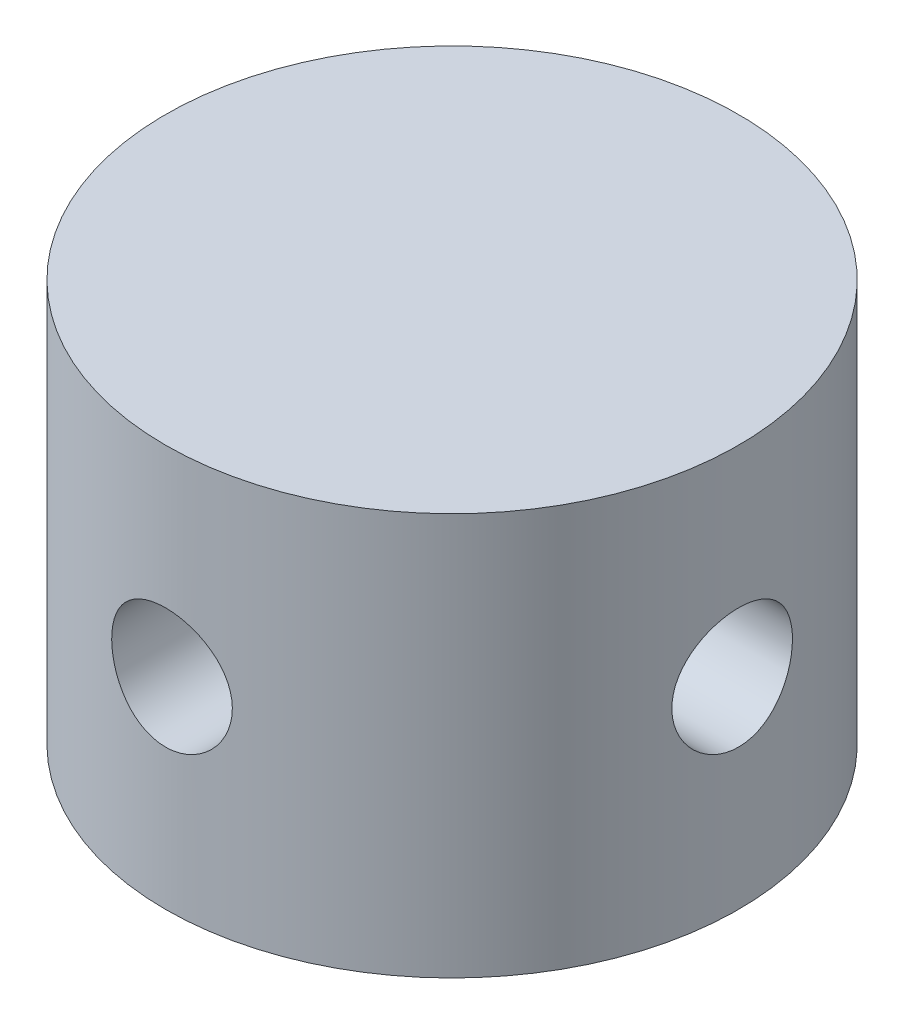
SolidWorks part; units mm, degrees
ref_plane "Front Plane" through (0, 0, 0) normal (0, 0, 1) x (1, 0, 0)
ref_plane "Top Plane" through (0, 0, 0) normal (0, 1, 0) x (1, 0, 0)
ref_plane "Right Plane" through (0, 0, 0) normal (1, 0, 0) x (0, 0, -1)
sketch "Sketch1" plane through (0, 0, 0) normal (0, 1, 0) x (1, 0, 0)
  circle A0 centre (0, 0) radius 14.25
  dimension "D1" = 28.5
extrude "Boss-Extrude1" add sketch "Sketch1" along normal blind 20
ref_plane "Plane1" through (14.25, 0, 0) normal (1, 0, 0) x (0, 0, -1)
ref_axis "Axis1" through (0, 20, 0) along (0, -1, 0)
sketch "Sketch2" plane through (14.25, 0, 0) normal (1, 0, 0) x (0, 0, -1)
  line L0 (0, 19.9907) -> (0, 0) construction
  line L1 (0, 20) -> (0, 0) construction
  circle A0 centre (0, 9.9954) radius 3
  dimension "D1" = 6
extrude "Cut-Extrude1" cut sketch "Sketch2" against normal blind 9
pattern_circular "CirPattern1" count 4 over 360 about axis through (0, 20, 0) along (0, -1, 0) of "Cut-Extrude1"
